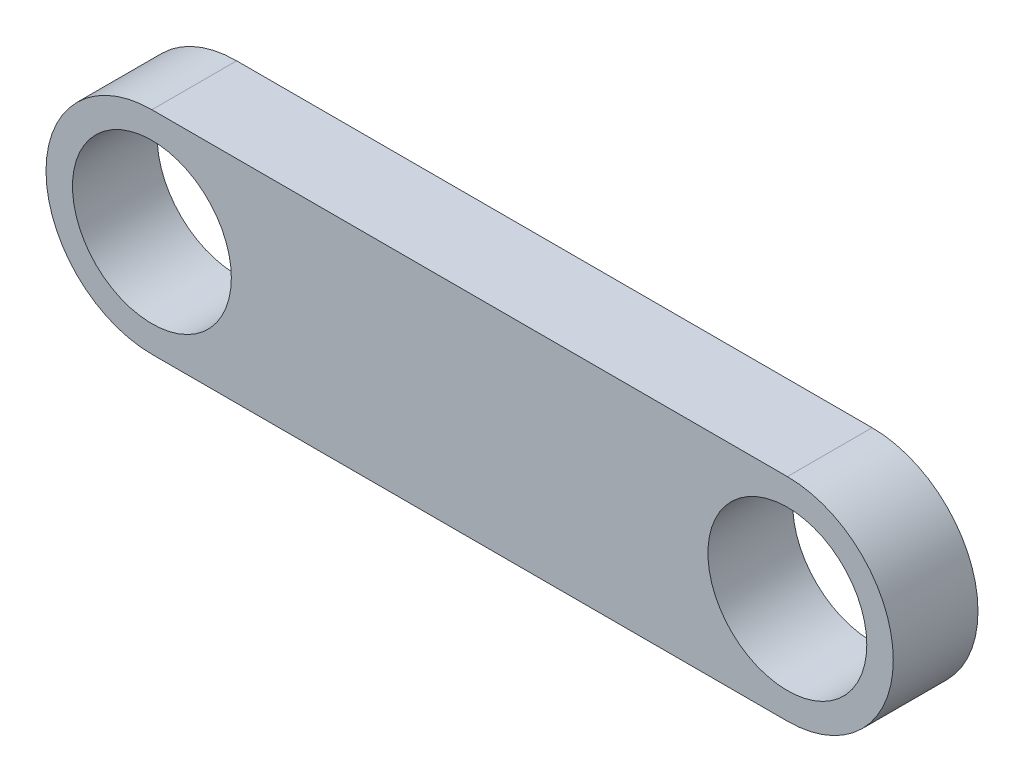
SolidWorks part; units mm, degrees
ref_plane "Front Plane" through (0, 0, 0) normal (0, 0, 1) x (1, 0, 0)
ref_plane "Top Plane" through (0, 0, 0) normal (0, 1, 0) x (1, 0, 0)
ref_plane "Right Plane" through (0, 0, 0) normal (1, 0, 0) x (0, 0, -1)
sketch "Sketch2" plane through (0, 0, 0) normal (0, 0, 1) x (1, 0, 0)
  line L0 (0, -100) -> (600, -100)
  line L1 (0, 100) -> (600, 100)
  line L4 (307.9864, -99.98) -> (307.9864, -99.9786)
  circle A0 centre (0, 0) radius 100
  circle A2 centre (600, 0) radius 100
extrude "Boss-Extrude1" add sketch "Sketch2" along normal blind 40 and the other way blind 40 contours A0 | A2 L1 A0 L0 | A2 region at (300, 0, 0) region at (0, 0, 0) region at (600, 0, 0)
sketch "Sketch7" plane through (0, 0, 0) normal (0, 0, 1) x (1, 0, 0)
  circle A0 centre (0, 0) radius 75
extrude "Cut-Extrude1" cut sketch "Sketch7" against normal blind 200 and the other way blind 200
sketch "Sketch8" plane through (0, 0, 0) normal (0, 0, 1) x (1, 0, 0)
  line L0 (0, -100) -> (300.7207, -100)
  line L1 (0, 100) -> (300.7207, 100)
  line L4 (307.9864, -99.98) -> (307.9864, -99.9786)
  circle A0 centre (0, 0) radius 100
  circle A2 centre (600, 0) radius 100
  circle A3 centre (600, 0) radius 75
extrude "Cut-Extrude2" cut sketch "Sketch8" against normal blind 200 and the other way blind 200 contours A3 | A3 region at (600, 0, 0)
